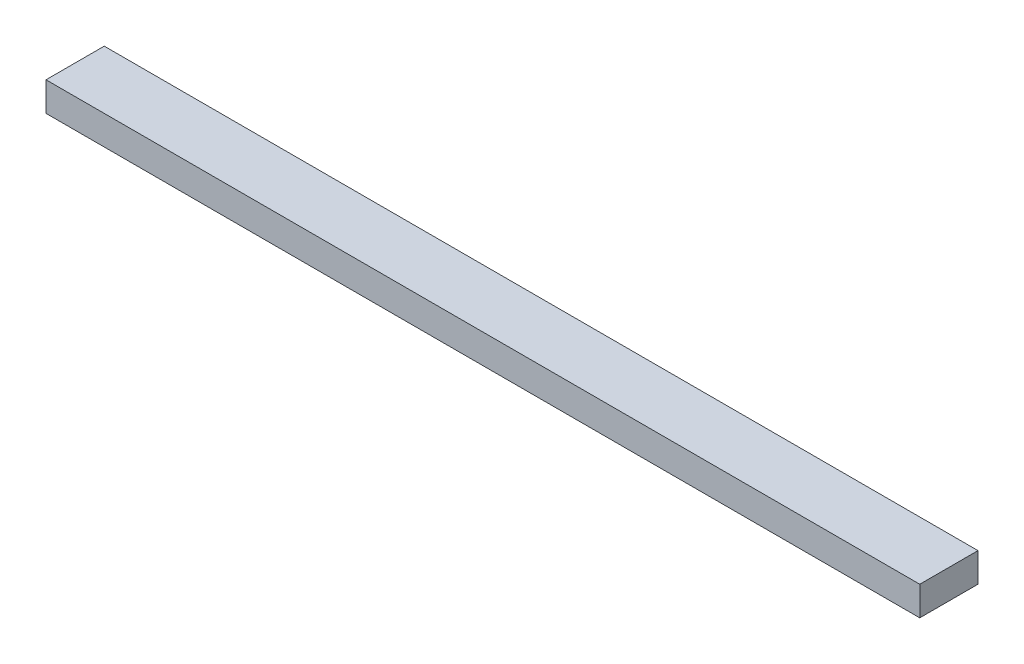
SolidWorks part; units mm, degrees
ref_plane "Front Plane" through (0, 0, 0) normal (0, 0, 1) x (1, 0, 0)
ref_plane "Top Plane" through (0, 0, 0) normal (0, 1, 0) x (1, 0, 0)
ref_plane "Right Plane" through (0, 0, 0) normal (1, 0, 0) x (0, 0, -1)
sketch "Sketch1" plane through (0, 0, 0) normal (0, 0, 1) x (1, 0, 0)
  line L0 (53.5799, -76.2) -> (-104.6669, -76.2) construction
  line L1 (90.6195, 6.35) -> (65.2195, 6.35) construction
  line L2 (90.6195, -158.75) -> (65.2195, -158.75) construction
  line L3 (90.6195, -152.4) -> (90.6195, 0) construction
  line L4 (65.2195, -14.2875) -> (-125.2805, -14.2875)
  line L5 (65.2195, -14.2875) -> (65.2195, -7.9375)
  line L6 (65.2195, -7.9375) -> (-125.2805, -7.9375)
  line L7 (-125.2805, -14.2875) -> (-125.2805, -7.9375)
  dimension "D1" = 6.35
  dimension "D2" = 123.825
  dimension "D3" = 190.5
  dimension "D4" = 25.4
extrude "Boss-Extrude1" add sketch "Sketch1" along normal blind 12.7
